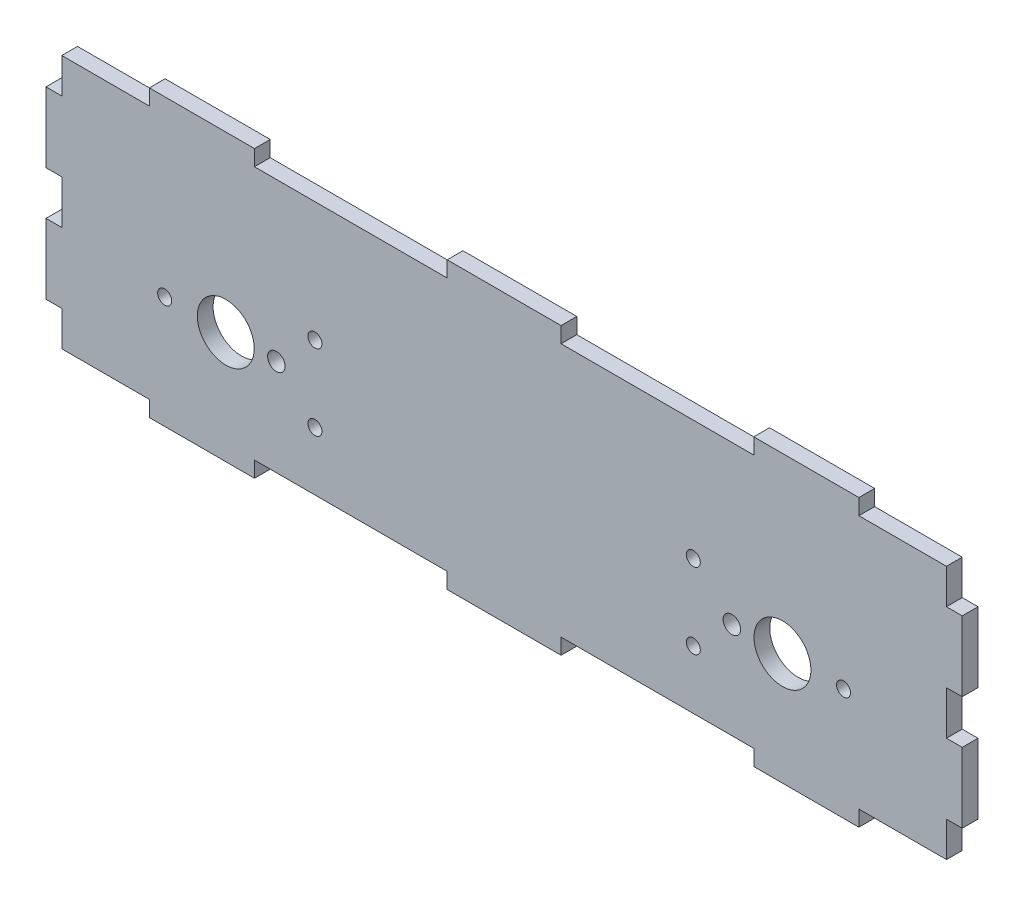
SolidWorks part; units mm, degrees
material "Бальса"
ref_plane "Спереди" through (0, 0, 0) normal (0, 0, 1) x (1, 0, 0)
ref_plane "Сверху" through (0, 0, 0) normal (0, 1, 0) x (1, 0, 0)
ref_plane "Справа" through (0, 0, 0) normal (1, 0, 0) x (0, 0, -1)
sketch "Эскиз1" plane through (0, 0, 0) normal (0, 0, 1) x (1, 0, 0)
  line L0 (170, 12) -> (0, 12) construction
  line L1 (0, 0) -> (170, 0)
  line L2 (0, 0) -> (0, 48)
  line L3 (0, 48) -> (170, 48)
  line L4 (170, 0) -> (170, 48)
  line L5 (41.8, 3.35) -> (41.8, 20.65) construction
  line L6 (41.8, 20.65) -> (128.2, 20.65) construction
  line L7 (128.2, 20.65) -> (128.2, 3.35) construction
  line L8 (128.2, 3.35) -> (41.8, 3.35) construction
  circle A0 centre (137, 12) radius 2
  circle A1 centre (33, 12) radius 2
  circle A2 centre (148.55, 12) radius 6.5
  circle A3 centre (21.45, 12) radius 6.5
  circle A4 centre (128.2, 20.65) radius 1.6
  circle A5 centre (128.2, 3.35) radius 1.6
  circle A6 centre (41.8, 20.65) radius 1.6
  circle A7 centre (41.8, 3.35) radius 1.6
  circle A16 centre (162.5, 12) radius 1.6
  circle A17 centre (148.55, 12) radius 2.65 construction
  circle A18 centre (7.5, 12) radius 1.6
  circle A19 centre (21.45, 12) radius 2.65 construction
  dimension "D3" = 4
  dimension "D5" = 104
  dimension "D7" = 13
  dimension "D8" = 11.55
  dimension "D9" = 13
  dimension "D10" = 11.55
  dimension "D15" = 3.2
  dimension "D24" = 13.95
  dimension "D25" = 3.2
  dimension "D26" = 13.95
  dimension "D27" = 3.2
  dimension "D1" = 48
  dimension "D2" = 170
  dimension "D4" = 12
  dimension "D6" = 33
  dimension "D11" = 86.4
  dimension "D12" = 17.3
  dimension "D13" = 3.35
  dimension "D14" = 41.8
base flange "Базовая кромка1" sketch "Эскиз1" thickness 3.6 reverse thickness direction no parameters "D1"=0.7366
sketch "Эскиз7" plane through (0, 0, -3.6) normal (0, 0, -1) x (-1, 0, 0)
  line L0 (-170, 0) -> (-170, 48) construction
  line L1 (-170, 48) -> (-186, 48)
  line L2 (-170, 48) -> (-170, 0)
  line L3 (-170, 0) -> (-186, 0)
  line L4 (-186, 48) -> (-186, 0)
  line L5 (0, 0) -> (16, 0)
  line L6 (0, 0) -> (0, 48)
  line L7 (0, 48) -> (16, 48)
  line L8 (16, 0) -> (16, 48)
  line L9 (0, 0) -> (-170, 0) construction
  dimension "D1" = 16
  dimension "D2" = 16
extrude "Бобышка-Вытянуть1" add sketch "Эскиз7" against normal up to surface (3.6 mm away) up to face at (9.1, 12, 0)
sketch "Эскиз8" plane through (0, 0, -3.6) normal (0, 0, -1) x (-1, 0, 0)
  line L1 (-186, 0) -> (16, 0)
  line L2 (-186, 0) -> (-186, -10)
  line L3 (-186, -10) -> (16, -10)
  line L4 (16, 0) -> (16, -10)
  dimension "D1" = 10
extrude "Бобышка-Вытянуть2" add sketch "Эскиз8" against normal up to surface (3.6 mm away) up to face at (9.1, 12, 0)
sketch "Эскиз9" plane through (0, 0, -3.6) normal (0, 0, -1) x (-1, 0, 0)
  line L0 (-186, 48) -> (-186, -10) construction
  line L1 (-189.6, 40) -> (-186, 40)
  line L2 (-189.6, 40) -> (-189.6, 24)
  line L3 (-189.6, 24) -> (-186, 24)
  line L4 (-186, 40) -> (-186, 24)
  line L5 (-186, 48) -> (16, 48) construction
  line L6 (-189.6, 14) -> (-186, 14)
  line L7 (-189.6, 14) -> (-189.6, -2)
  line L8 (-189.6, -2) -> (-186, -2)
  line L9 (-186, 14) -> (-186, -2)
  line L10 (-166, 48) -> (-142, 48)
  line L11 (-166, 48) -> (-166, 51.6)
  line L12 (-166, 51.6) -> (-142, 51.6)
  line L13 (-142, 48) -> (-142, 51.6)
  line L14 (16, -10) -> (16, 48) construction
  line L15 (-98, 48) -> (-72, 48)
  line L16 (-98, 48) -> (-98, 51.6)
  line L17 (-98, 51.6) -> (-72, 51.6)
  line L18 (-72, 48) -> (-72, 51.6)
  line L19 (-28, 48) -> (-4, 48)
  line L20 (-28, 48) -> (-28, 51.6)
  line L21 (-28, 51.6) -> (-4, 51.6)
  line L22 (-4, 48) -> (-4, 51.6)
  line L23 (16, 40) -> (19.6, 40)
  line L24 (16, 40) -> (16, 24)
  line L25 (16, 24) -> (19.6, 24)
  line L26 (19.6, 40) -> (19.6, 24)
  line L27 (-186, -10) -> (16, -10) construction
  line L28 (16, 14) -> (19.6, 14)
  line L29 (16, 14) -> (16, -2)
  line L30 (16, -2) -> (19.6, -2)
  line L31 (19.6, 14) -> (19.6, -2)
  line L32 (-28, -10) -> (-4, -10)
  line L33 (-28, -10) -> (-28, -13.6)
  line L34 (-28, -13.6) -> (-4, -13.6)
  line L35 (-4, -10) -> (-4, -13.6)
  line L36 (-186, 19) -> (16, 19) construction
  line L37 (-98, -10) -> (-72, -10)
  line L38 (-98, -10) -> (-98, -13.6)
  line L39 (-98, -13.6) -> (-72, -13.6)
  line L40 (-72, -10) -> (-72, -13.6)
  line L41 (-166, -10) -> (-142, -10)
  line L42 (-166, -10) -> (-166, -13.6)
  line L43 (-166, -13.6) -> (-142, -13.6)
  line L44 (-142, -10) -> (-142, -13.6)
  line L45 (-85, 19) -> (-85, 51.6) construction
  line L46 (-85, 19) -> (-85, -13.6) construction
  dimension "D1" = 20
  dimension "D2" = 10
  dimension "D3" = 5
  dimension "D4" = 8
  dimension "D5" = 8
  dimension "D6" = 3.6
  dimension "D7" = 3.6
  dimension "D8" = 20
  dimension "D9" = 44
  dimension "D10" = 44
  dimension "D11" = 3.6
  dimension "D12" = 3.6
  dimension "D13" = 24
extrude "Бобышка-Вытянуть3" add sketch "Эскиз9" against normal up to surface (3.6 mm away) up to face at (9.1, 12, 0)
sketch "Сгиб-Линии1" plane through (0, 0, 0) normal (0, 1, 0) x (1, 0, 0)
sketch "Граничная рамка1" plane through (0, 0, 0) normal (0, 1, 0) x (1, 0, 0)
sheet metal parameters "Листовой металл3" thickness 3.6 parameters "D1"=0.7366
flat pattern "Развертка3" [suppressed]
sketch "Сгиб-Линии2" plane through (0, 0, 0) normal (0, 1, 0) x (1, 0, 0)
sketch "Граничная рамка2" [suppressed] plane through (0, 0, 0) normal (0, 1, 0) x (1, 0, 0)
sheet metal parameters "Листовой металл5" thickness 3.6 parameters "D1"=0.7366
flat pattern "Развертка3"
sketch "Сгиб-Линии2" plane through (0, 0, 0) normal (0, 1, 0) x (1, 0, 0)
sketch "Граничная рамка2" [suppressed] plane through (0, 0, 0) normal (0, 1, 0) x (1, 0, 0)
sheet metal parameters "Листовой металл6" thickness 3.6 parameters "D1"=0.7366
flat pattern "Развертка3"
sketch "Сгиб-Линии2" plane through (0, 0, 0) normal (0, 1, 0) x (1, 0, 0)
sketch "Граничная рамка2" [suppressed] plane through (0, 0, 0) normal (0, 1, 0) x (1, 0, 0)
sheet metal parameters "Листовой металл7" thickness 3.6 parameters "D1"=0.7366
flat pattern "Развертка3"
sketch "Сгиб-Линии2" plane through (0, 0, 0) normal (0, 1, 0) x (1, 0, 0)
sketch "Граничная рамка2" [suppressed] plane through (0, 0, 0) normal (0, 1, 0) x (1, 0, 0)
